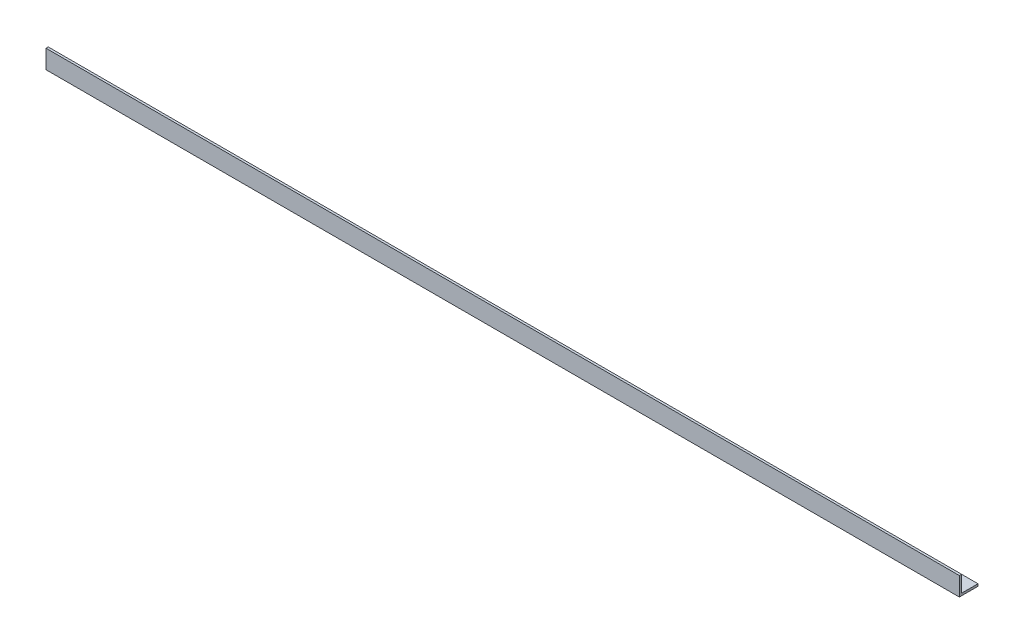
SolidWorks part; units mm, degrees
ref_plane "Спереди" through (0, 0, 0) normal (0, 0, 1) x (1, 0, 0)
ref_plane "Сверху" through (0, 0, 0) normal (0, 1, 0) x (1, 0, 0)
ref_plane "Справа" through (0, 0, 0) normal (1, 0, 0) x (0, 0, -1)
sketch "Эскиз1" plane through (0, 0, 0) normal (1, 0, 0) x (0, 0, -1)
  line L0 (0, 0) -> (50, 0)
  line L5 (0, 50) -> (0, 0)
extrude "Вытянуть-Тонкостенный2" add sketch "Эскиз1" along normal blind 2450 thin thin type one direction reverse wall 6
